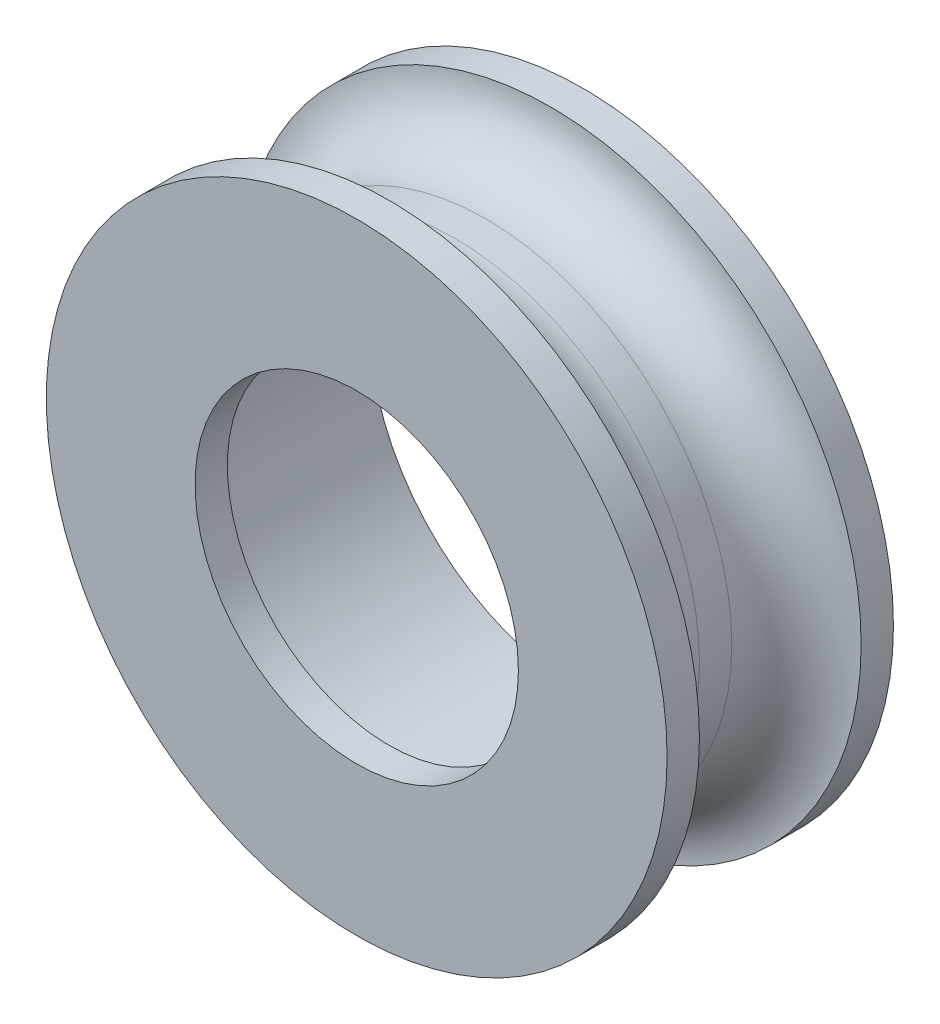
SolidWorks part; units mm, degrees
ref_plane "Alzado" through (0, 0, 0) normal (0, 0, 1) x (1, 0, 0)
ref_plane "Planta" through (0, 0, 0) normal (0, 1, 0) x (1, 0, 0)
ref_plane "Vista lateral" through (0, 0, 0) normal (1, 0, 0) x (0, 0, -1)
sketch "Croquis1" plane through (0, 0, 0) normal (0, 0, 1) x (1, 0, 0)
  circle A0 centre (0, 0) radius 6.6
  circle A1 centre (0, 0) radius 7.6
  dimension "D1" = 13.2
  dimension "D2" = 1
extrude "Saliente-Extruir1" add sketch "Croquis1" along normal blind 5
sketch "Croquis3" plane through (0, 0, 5) normal (0, 0, 1) x (1, 0, 0)
  circle A0 centre (0, 0) radius 5
  circle A1 centre (0, 0) radius 6.6 construction
  circle A2 centre (0, 0) radius 6.6
  circle A3 centre (0, 0) radius 9.6
  circle M1 centre (0, 0) radius 7.6
  circle M2 centre (0, 0) radius 6.6
  dimension "D1" = 3
  dimension "4mm" = 10
extrude "Saliente-Extruir2" add sketch "Croquis3" along normal blind 1 contours A3 M1 | A0 M2 | M1 M2 region at (-6.4133, 0, 5) region at (-9.3285, 0, 5) region at (-7.385, 0, 5)
extrude "Boss-Extrude1" add sketch "Croquis3<4>" against normal blind 1 from surface contours A3 M1 | M1 M2 region at (-9.3285, 0, 5) region at (-7.385, 0, 5) starting at face at (7.6, 0, 0)
sketch "Croquis3<4>" plane through (0, 0, 5) normal (0, 0, 1) x (1, 0, 0) same geometry as "Croquis3"
fillet "Redondeo1" radius 2 2 edges at (7.6, 0, 0) (7.6, 0, 5)
